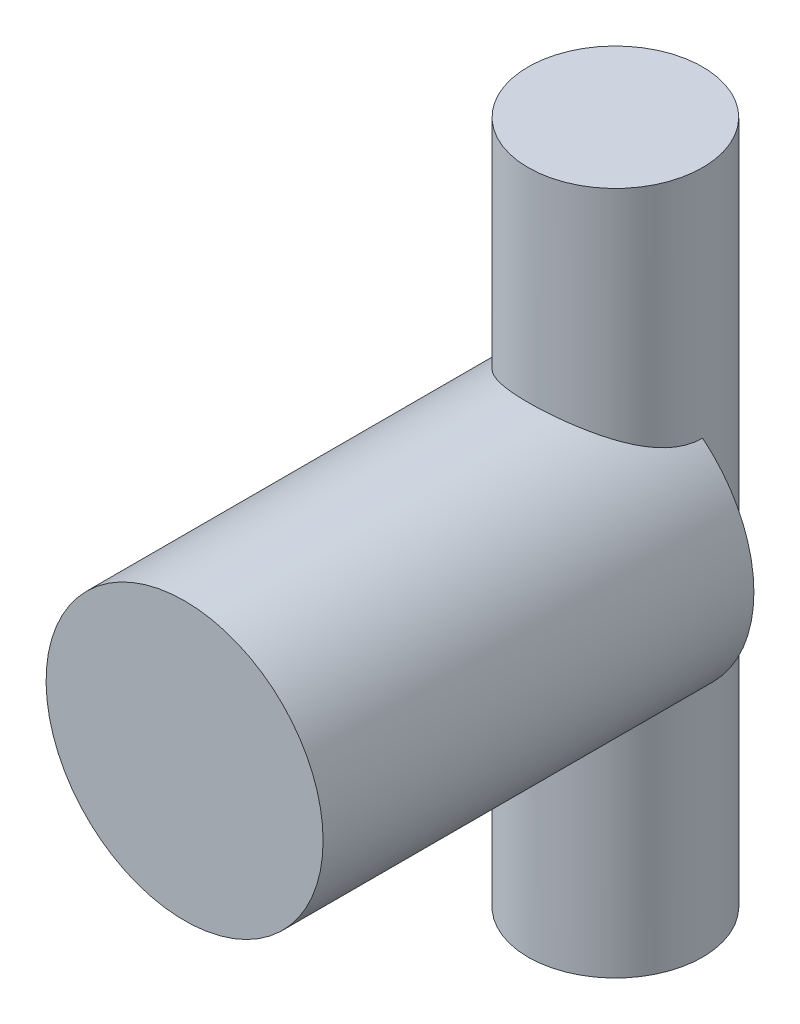
SolidWorks part; units mm, degrees
material "Brass"
ref_plane "Front Plane" through (0, 0, 0) normal (0, 0, 1) x (1, 0, 0)
ref_plane "Top Plane" through (0, 0, 0) normal (0, 1, 0) x (1, 0, 0)
ref_plane "Right Plane" through (0, 0, 0) normal (1, 0, 0) x (0, 0, -1)
sketch "Sketch1" plane through (0, 0, 0) normal (0, 1, 0) x (1, 0, 0)
  circle A0 centre (0, 0) radius 8
  dimension "D1" = 16
extrude "Boss-Extrude1" add sketch "Sketch1" along normal blind 31.35 and the other way blind 31.35
sketch "Sketch2" plane through (0, 0, 0) normal (0, 0, 1) x (1, 0, 0)
  circle A0 centre (0, 0) radius 12.7
  dimension "D1" = 25.4
extrude "Boss-Extrude2" add sketch "Sketch2" along normal blind 39.5
